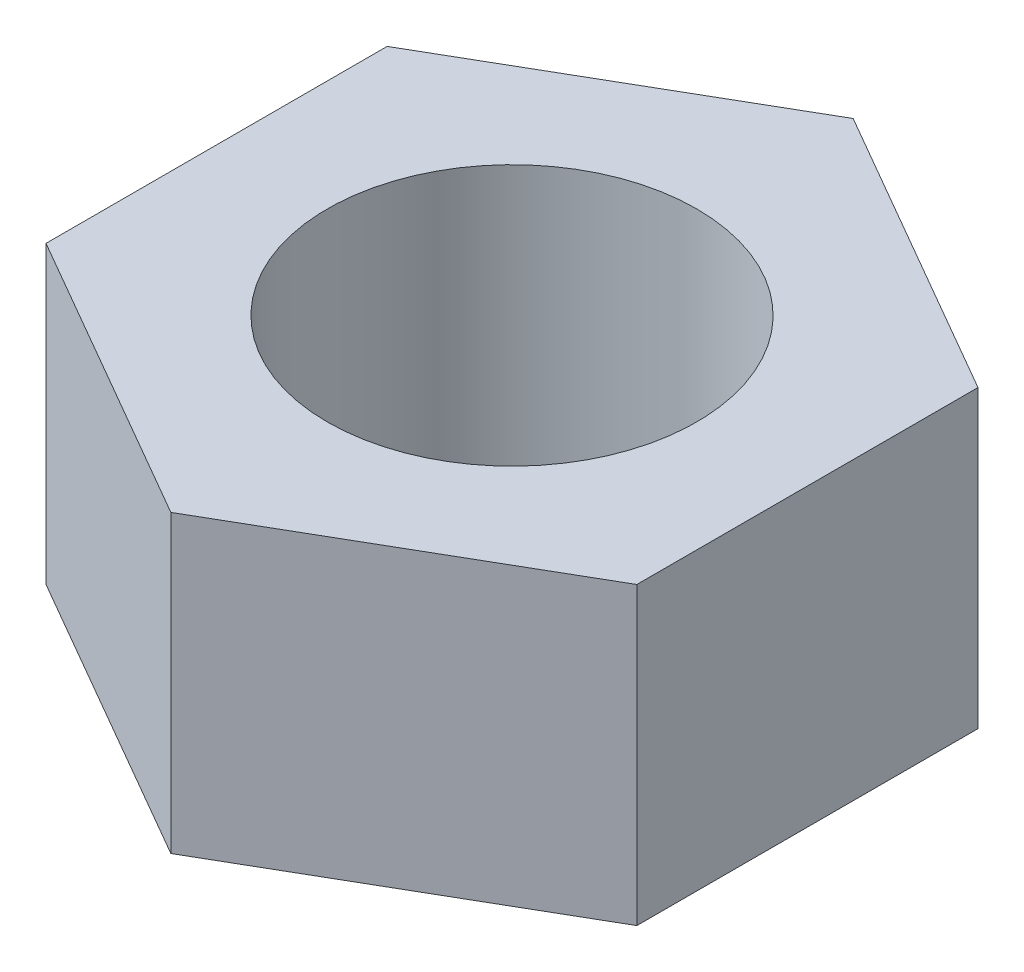
SolidWorks part; units mm, degrees
ref_plane "Front Plane" through (0, 0, 0) normal (0, 0, 1) x (1, 0, 0)
ref_plane "Top Plane" through (0, 0, 0) normal (0, 1, 0) x (1, 0, 0)
ref_plane "Right Plane" through (0, 0, 0) normal (1, 0, 0) x (0, 0, -1)
sketch "Sketch1" plane through (0, 0, 0) normal (0, 1, 0) x (1, 0, 0)
  line L0 (0, 65.635) -> (0, -82.8445) construction
  line L1 (-105.9574, 0) -> (126.8235, 0) construction
  line L2 (-4, 2.3094) -> (-4, -2.3094)
  line L3 (4, 2.3094) -> (4, -2.3094)
  line L4 (-4, 2.3094) -> (0, 4.6188)
  line L5 (-4, -2.3094) -> (0, -4.6188)
  line L6 (0, 4.6188) -> (4, 2.3094)
  line L7 (-2, 3.4641) -> (2, -3.4641) construction
  line L8 (4, -2.3094) -> (0, -4.6188)
  line L9 (4, 2.3094) -> (4.0054, 2.3366) construction
  circle A0 centre (0, 0) radius 2.5
  circle A1 centre (0, 0) radius 4 construction
  dimension "D1" = 8
  dimension "D2" = 5
extrude "Boss-Extrude1" add sketch "Sketch1" along normal blind 2 and the other way blind 2
